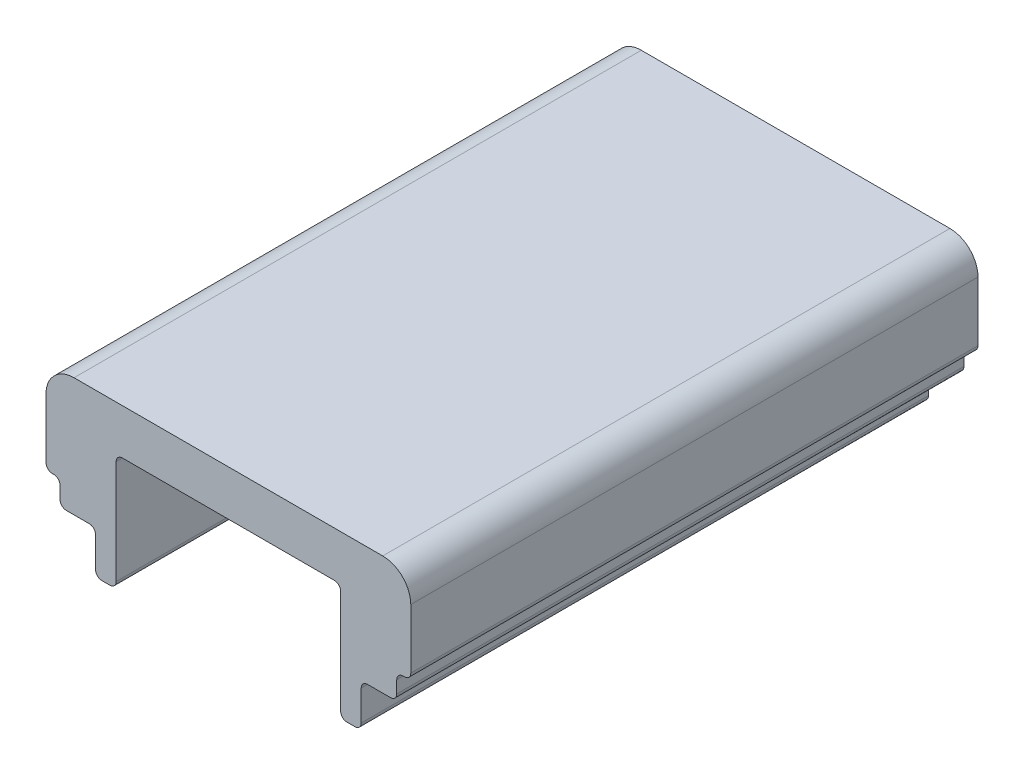
SolidWorks part; units mm, degrees
material "Pink Foam"
ref_plane "Front Plane" through (0, 0, 0) normal (0, 0, 1) x (1, 0, 0)
ref_plane "Top Plane" through (0, 0, 0) normal (0, 1, 0) x (1, 0, 0)
ref_plane "Right Plane" through (0, 0, 0) normal (1, 0, 0) x (0, 0, -1)
sketch "Sketch1" plane through (0, 0, 0) normal (0, 0, 1) x (1, 0, 0)
  line L0 (-101.6, 19.0868) -> (-165.1, 19.0868) construction
  line L1 (-159.385, 0) -> (-158.115, 0)
  line L2 (-165.1, 5.715) -> (-165.1, 59.52)
  line L3 (-139.7, 84.92) -> (139.7, 84.92)
  line L4 (165.1, 5.715) -> (165.1, 59.52)
  line L6 (-101.6, 0) -> (-101.6, 38.1735)
  line L7 (-95.885, 43.8885) -> (95.885, 43.8885)
  line L8 (101.6, 0) -> (101.6, 38.1735)
  line L9 (101.6, 19.0868) -> (165.1, 19.0868) construction
  line L12 (-101.6, 0) -> (-101.6, -55.82)
  line L13 (-107.315, -61.535) -> (-114.53, -61.535)
  line L14 (-120.245, -28.34) -> (-120.245, -55.82)
  line L17 (-125.96, -22.625) -> (-146.685, -22.625)
  line L18 (-152.4, -5.715) -> (-152.4, -16.91)
  line L19 (0, 0) -> (0, 43.8885) construction
  line L20 (101.6, 0) -> (101.6, -55.82)
  line L21 (107.315, -61.535) -> (114.53, -61.535)
  line L22 (120.245, -28.34) -> (120.245, -55.82)
  line L23 (125.96, -22.625) -> (146.685, -22.625)
  line L24 (152.4, -5.715) -> (152.4, -16.91)
  line L25 (158.115, 0) -> (159.385, 0)
  arc A0 (139.7, 84.92) -> (165.1, 59.52) centre (139.7, 59.52) cw
  arc A1 (-165.1, 59.52) -> (-139.7, 84.92) centre (-139.7, 59.52) cw
  arc A2 (95.885, 43.8885) -> (101.6, 38.1735) centre (95.885, 38.1735) cw
  arc A3 (-101.6, 38.1735) -> (-95.885, 43.8885) centre (-95.885, 38.1735) cw
  arc A4 (-159.385, 0) -> (-165.1, 5.715) centre (-159.385, 5.715) cw
  arc A5 (159.385, 0) -> (165.1, 5.715) centre (159.385, 5.715) ccw
  arc A6 (152.4, -5.715) -> (158.115, 0) centre (158.115, -5.715) cw
  arc A7 (146.685, -22.625) -> (152.4, -16.91) centre (146.685, -16.91) ccw
  arc A8 (120.245, -28.34) -> (125.96, -22.625) centre (125.96, -28.34) cw
  arc A9 (114.53, -61.535) -> (120.245, -55.82) centre (114.53, -55.82) ccw
  arc A10 (101.6, -55.82) -> (107.315, -61.535) centre (107.315, -55.82) ccw
  arc A11 (-101.6, -55.82) -> (-107.315, -61.535) centre (-107.315, -55.82) cw
  arc A12 (-114.53, -61.535) -> (-120.245, -55.82) centre (-114.53, -55.82) cw
  arc A13 (-146.685, -22.625) -> (-152.4, -16.91) centre (-146.685, -16.91) cw
  arc A14 (-158.115, 0) -> (-152.4, -5.715) centre (-158.115, -5.715) cw
  arc A15 (-120.245, -28.34) -> (-125.96, -22.625) centre (-125.96, -28.34) ccw
  point P15 (165.1, 84.92)
  point P18 (-165.1, 84.92)
  point P34 (101.6, 43.8885)
  point P37 (-101.6, 43.8885)
  point P40 (-165.1, 0)
  point P45 (152.4, 0)
  point P48 (152.4, -22.625)
  point P51 (120.245, -22.625)
  point P54 (120.245, -61.535)
  point P57 (101.6, -61.535)
  point P60 (-101.6, -61.535)
  point P63 (-120.245, -61.535)
  point P66 (-152.4, -22.625)
  point P69 (-152.4, 0)
  point P72 (-120.245, -22.625)
  dimension "D5" = 25.4
  dimension "D10" = 5.715
  dimension "D1" = 84.92
  dimension "D2" = 330.2
  dimension "D3" = 203.2
  dimension "D4" = 43.8885
  dimension "D6" = 61.535
  dimension "D7" = 18.645
  dimension "D8" = 12.7
  dimension "D9" = 22.625
  dimension "D11" = 43.8885
  dimension "D13" = 1.27
extrude "Boss-Extrude1" add sketch "Sketch1" along normal blind 513.461 contours L8 L1 L4 L3 L2 L6 L7 region at (-160.8719, 4.2281, 0)
